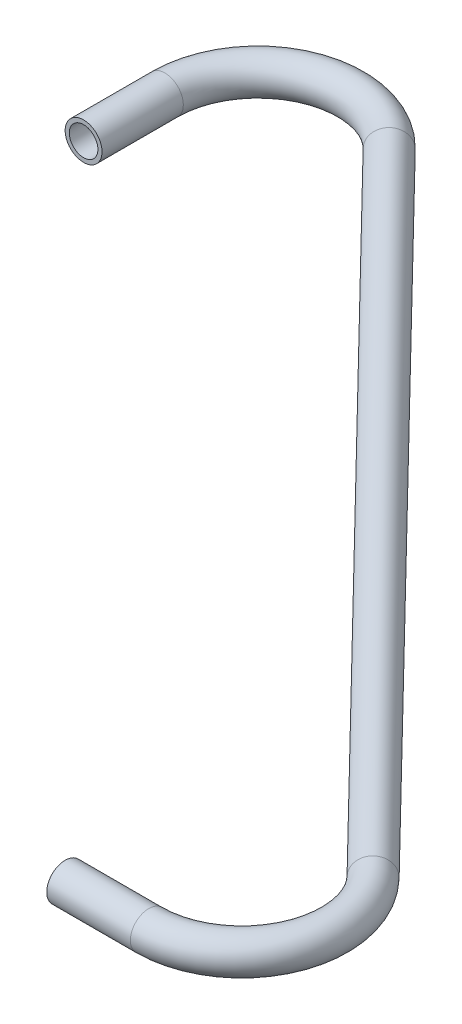
SolidWorks part; units mm, degrees
ref_plane "Front Plane" through (0, 0, 0) normal (0, 0, 1) x (1, 0, 0)
ref_plane "Top Plane" through (0, 0, 0) normal (0, 1, 0) x (1, 0, 0)
ref_plane "Right Plane" through (0, 0, 0) normal (1, 0, 0) x (0, 0, -1)
sketch3d "3DSketch1"
  line L0 (0, 0, 0) -> (14.4032, 0, 0)
  line L1 (25.8603, 0, -27.1684) -> (-81.3746, 0, -137.1752)
  line L3 (-108.8318, 0, -126.0068) -> (-108.8318, 0, -112.0068)
  arc A0 (-108.8318, 0, -126.0068) -> (-81.3746, 0, -137.1752) centre (-92.8318, 0, -126.0068) ccw
  arc A2 (14.4032, 0, 0) -> (25.8603, 0, -27.1684) centre (14.4032, 0, -16) ccw
  point P3 (0, 0, 0)
  point P8 (0, 0, 0)
  point P9 (-92.8318, -16, -126.0068)
  point P10 (0, 0, 0)
  point P11 (0, 0, 0)
  point P12 (0, 0, 0)
  point P13 (0, 0, 0)
  point P17 (14.4032, 16, -16)
  dimension "D5" = 16
  dimension "D7" = 16
  dimension "D1" = 108.8318
  dimension "D6" = 153.6256
  dimension "D2" = 156.1726
  dimension "D3" = 14
  dimension "D4" = 14.4032
sketch "Sketch2" plane through (0, 0, 0) normal (1, 0, 0) x (0, 0, -1)
  circle A0 centre (0, 0) radius 3.175
  dimension "D1" = 6.35
sweep "Sweep-Thin1" add profiles "Sketch2" path "3DSketch1" parameters "D1"=0.7112
